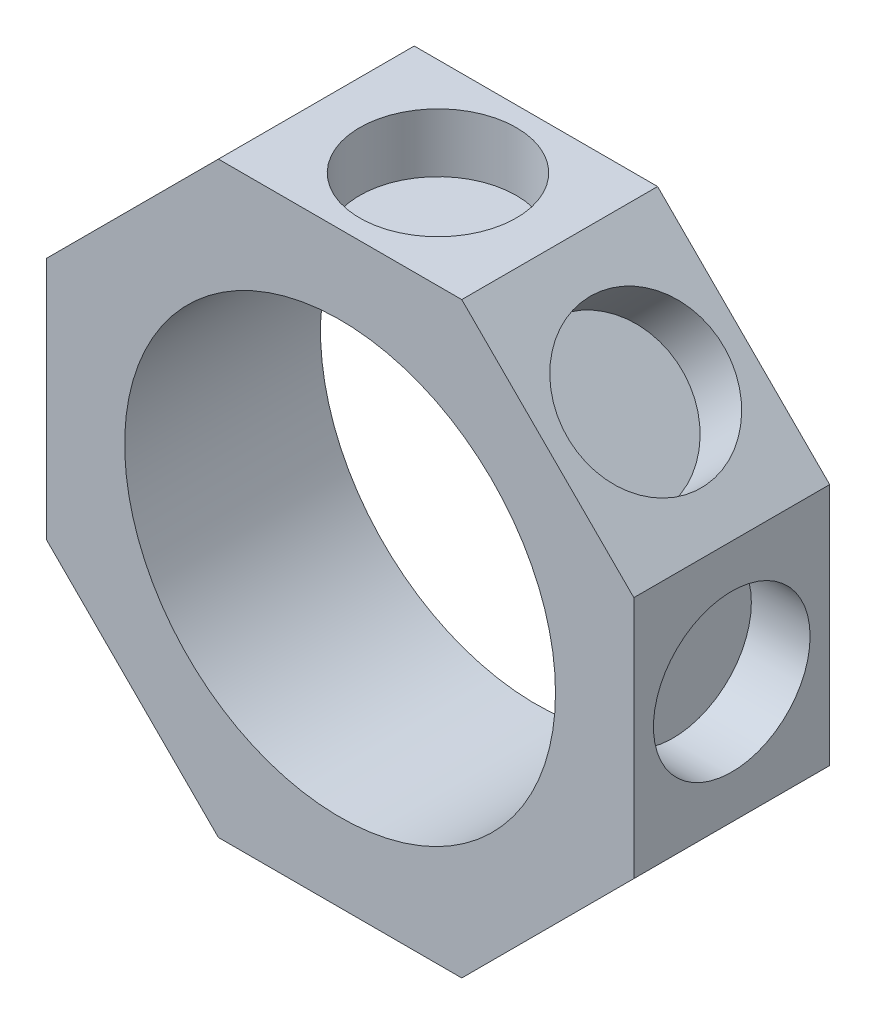
SolidWorks part; units mm, degrees
ref_plane "Top Plane" through (0, 0, 0) normal (0, 0, 1) x (1, 0, 0)
ref_plane "Right Plane" through (0, 0, 0) normal (0, 1, 0) x (1, 0, 0)
ref_plane "Front Plane" through (0, 0, 0) normal (1, 0, 0) x (0, 0, -1)
ref_axis "x-axis" through (-88.99, 0, 0) along (1, 0, 0)
ref_axis "y-axis" through (0, -55, 0) along (0, 1, 0)
ref_axis "z-axis" through (0, 0, 55) along (0, 0, -1)
sketch "Sketch1" plane through (0, 0, 0) normal (0, 0, 1) x (1, 0, 0)
  line L0 (6.2132, 15) -> (-6.2132, 15)
  line L1 (-15, 6.2132) -> (-15, -6.2132)
  line L2 (-15, -6.2132) -> (-6.2132, -15)
  line L3 (-6.2132, -15) -> (6.2132, -15)
  line L4 (6.2132, -15) -> (15, -6.2132)
  line L5 (15, -6.2132) -> (15, 6.2132)
  line L6 (15, 6.2132) -> (6.2132, 15)
  line L7 (-6.2132, 15) -> (-15, 6.2132)
  line L8 (-15, 0) -> (0, 0) construction
  circle A0 centre (0, 0) radius 11
  circle A1 centre (0, 0) radius 15 construction
  point P13 (2.4227, -5.8489)
  dimension "D1" = 22
  dimension "D2" = 15
extrude "Boss-Extrude1" add sketch "Sketch1" along normal mid plane 10
sketch "Sketch2" plane through (0, -15, 0) normal (0, -1, 0) x (-1, 0, 0)
  circle A0 centre (0, 0) radius 4
  dimension "D1" = 8
extrude "Cut-Extrude3" cut sketch "Sketch2" against normal blind 3
pattern_circular "CirPattern1" count 8 over 360 about axis through (0, 0, 5) along (0, 0, 1) of "Cut-Extrude3"
